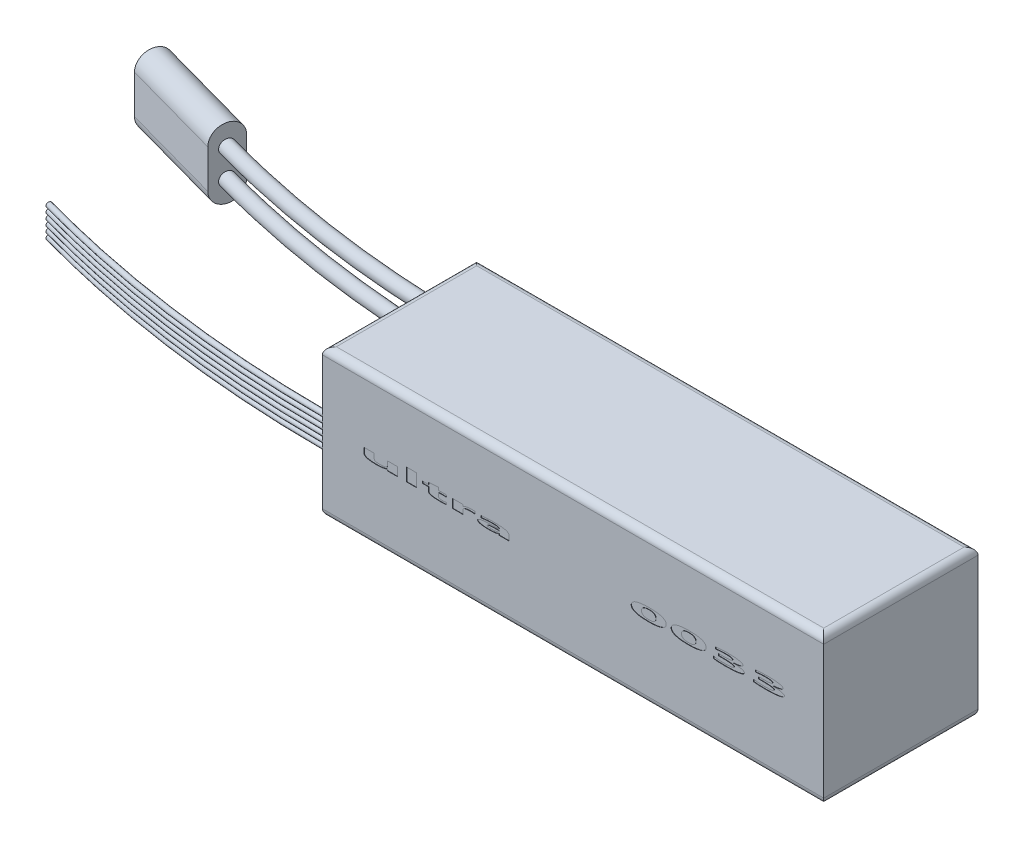
SolidWorks part; units mm, degrees
ref_plane "前视基准面" through (0, 0, 0) normal (0, 0, 1) x (1, 0, 0)
ref_plane "上视基准面" through (0, 0, 0) normal (0, 1, 0) x (1, 0, 0)
ref_plane "右视基准面" through (0, 0, 0) normal (1, 0, 0) x (0, 0, -1)
sketch "草图1" plane through (0, 0, 0) normal (0, 0, 1) x (1, 0, 0)
  line L0 (0, 39.7894) -> (0, -38.97) construction
  line L1 (-82.6952, 0) -> (84.8103, 0) construction
  line L3 (-71.5, 21) -> (71.5, 21)
  line L4 (-71.5, 21) -> (-71.5, -21)
  line L5 (-71.5, -21) -> (71.5, -21)
  line L6 (71.5, 21) -> (71.5, -21)
  line L7 (-71.5, 21) -> (71.5, -21) construction
  line L8 (-71.5, -21) -> (71.5, 21) construction
  arc A0 (-71.5, 21) -> (71.5, 21) centre (0, -487.725) cw
  arc A1 (-71.5, -21) -> (71.5, -21) centre (0, 487.725) ccw
  point P5 (0, 0)
  point P12 (0, 26)
  point P13 (0, -26)
  dimension "D1" = 52
  dimension "D2" = 42
  dimension "D3" = 143
extrude "凸台-拉伸1" add sketch "草图1" along normal mid plane 44 contours L6 L3 L4 L5 region at (0, 0, 0)
sketch "草图2" plane through (-71.5, 0, 0) normal (-1, 0, 0) x (0, 0, 1)
  line L0 (-44.5966, 0) -> (43.449, 0) construction
  line L1 (-22, 21) -> (-22, -21) construction
  line L2 (22, 21) -> (22, -21) construction
  circle A0 centre (-20, 4) radius 2
  circle A1 centre (21.25, 0.8) radius 0.75
  circle A2 centre (21.25, 2.4) radius 0.75
  circle A3 centre (21.25, 4) radius 0.75
  circle A4 centre (21.25, -0.8) radius 0.75
  circle A5 centre (21.25, -2.4) radius 0.75
  circle A6 centre (21.25, -4) radius 0.75
  circle A7 centre (-20, -4) radius 2
  dimension "D1" = 4
  dimension "D2" = 1.5
  dimension "D5" = 3
  dimension "D3" = 8
  dimension "D4" = 0.8
  dimension "D6" = 1.6
sketch "草图3" plane through (0, 0, 0) normal (0, 1, 0) x (1, 0, 0)
  line L1 (-71.5, -22) -> (-71.5, 22) construction
  line L2 (-119.5685, 20) -> (-71.5, 20) construction
  line L3 (0, 0) -> (-96.3982, 0) construction
  line L4 (-71.5, -21.25) -> (-100.5536, -21.25) construction
  arc A0 (-71.5, 20) -> (-151.5, 30.8634) centre (-71.5, 320) cw
  arc A1 (-71.5, -21.25) -> (-131.5, -27.3112) centre (-71.5, -321.25) ccw
  point P2 (-71.5, 20)
  point P4 (-71.5, -21.25)
  dimension "D2" = 300
  dimension "D3" = 60
  dimension "D4" = 300
  dimension "D1" = 80
sweep "扫描2" add profiles "草图2" path "草图3"
sketch "草图32" plane through (0, 0, 22) normal (0, 0, 1) x (1, 0, 0)
  text T0 "<b>ultra      0033</b>" font "微软雅黑" height 3.5
extrude "切除-拉伸1" cut sketch "草图32" against normal blind 0.1
sketch "草图33" plane through (-148.6589, 0, -41.1318) normal (-0.9638, 0, -0.2667) x (-0.2667, 0, 0.9638)
  line L0 (-5.8214, 0) -> (29.2876, 0) construction
  line L1 (10.6542, 6) -> (10.6542, -6) construction
  line L2 (10.6542, -5.5) -> (10.6542, 5.5) construction
  line L3 (6.1542, -5.5) -> (6.1542, 5.5)
  line L4 (15.1542, -5.5) -> (15.1542, 5.5)
  arc A0 (6.1542, -5.5) -> (15.1542, -5.5) centre (10.6542, -5.5) ccw
  arc A1 (15.1542, 5.5) -> (6.1542, 5.5) centre (10.6542, 5.5) ccw
  point P9 (10.6542, 0)
  dimension "D1" = 11
  dimension "D2" = 9
extrude "凸台-拉伸3" add sketch "草图33" along normal blind 30
mirror "镜向1" about plane through (0, 0, 0) normal (0, 0, 1) of "切除-拉伸1"
fillet "圆角1" radius 2 8 edges at (-71.5, -21, 0) (0, -21, 22) (71.5, -21, 0) (0, -21, -22) (71.5, 21, 0) (0, 21, 22) (-71.5, 21, 0) (0, 21, -22)
